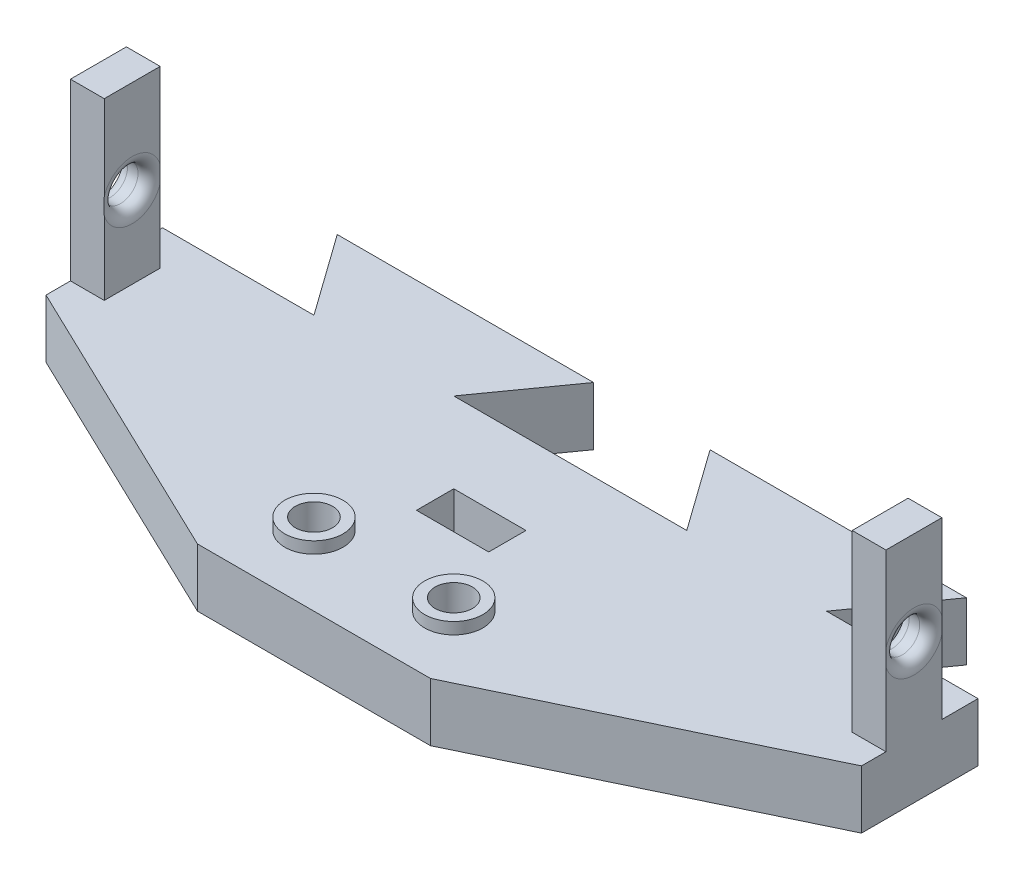
SolidWorks part; units mm, degrees
ref_plane "Front Plane" through (0, 0, 0) normal (0, 0, 1) x (1, 0, 0)
ref_plane "Top Plane" through (0, 0, 0) normal (0, 1, 0) x (1, 0, 0)
ref_plane "Right Plane" through (0, 0, 0) normal (1, 0, 0) x (0, 0, -1)
sketch "Sketch1" plane through (0, 0, 0) normal (0, 1, 0) x (1, 0, 0)
  line L0 (0, 0) -> (20, 0)
  line L1 (10, 0) -> (10, 12) construction
  line L2 (10, 12) -> (-25, 12) construction
  line L3 (0, 0) -> (-25, 12)
  line L4 (-25, 12) -> (-25, 22)
  line L5 (-25, 22) -> (45, 22)
  line L6 (45, 22) -> (45, 12)
  line L7 (45, 12) -> (20, 0)
  dimension "D1" = 35
  dimension "D2" = 20
  dimension "D3" = 12
  dimension "D4" = 70
  dimension "D5" = 10
  dimension "D6" = 10
extrude "Boss-Extrude1" add sketch "Sketch1" along normal blind 5
sketch "Sketch2" plane through (0, 5, 0) normal (0, 1, 0) x (1, 0, 0)
  line L0 (10, 0) -> (10, 22) construction
  line L1 (0, 0) -> (20, 0) construction
  line L2 (45, 22) -> (-25, 22) construction
  circle A0 centre (4, 6) radius 1.6
  circle A1 centre (16, 6) radius 1.6
  dimension "D1" = 3.2
  dimension "D2" = 6
  dimension "D3" = 6
extrude "Cut-Extrude1" cut sketch "Sketch2" against normal blind 3
ref_plane "Plane1" through (0, 0, -6) normal (0, 0, 1) x (1, 0, 0)
sketch "Sketch9" plane through (0, 5, 0) normal (0, 1, 0) x (1, 0, 0)
  line L0 (10, 0) -> (10, 22) construction
  line L1 (0, 0) -> (20, 0) construction
  line L2 (45, 22) -> (-25, 22) construction
  line L3 (10, 11.9) -> (-25, 11.9) construction
  line L4 (-25, 22) -> (-25, 12) construction
  line L5 (-2.75, 6) -> (2.75, 6) construction
  line L7 (6.9, 11.9) -> (13.1, 11.9)
  line L8 (6.9, 11.9) -> (6.9, 15.1)
  line L9 (6.9, 15.1) -> (13.1, 15.1)
  line L10 (13.1, 11.9) -> (13.1, 15.1)
  dimension "D1" = 5.9
  dimension "D2" = 3.1
  dimension "D3" = 3.1
  dimension "D4" = 3.2
sketch "Sketch10" plane through (0, 5, 0) normal (0, 1, 0) x (1, 0, 0)
  line L0 (-25, 22) -> (-25, 12) construction
  line L1 (-25, 18.9) -> (-22.1, 18.9)
  line L2 (-25, 18.9) -> (-25, 14.1)
  line L3 (-25, 14.1) -> (-22.1, 14.1)
  line L4 (-22.1, 18.9) -> (-22.1, 14.1)
  line L5 (45, 22) -> (-25, 22) construction
  line L6 (10, 22) -> (10, 0) construction
  line L7 (0, 0) -> (20, 0) construction
  line L8 (45, 14.1) -> (42.1, 14.1)
  line L9 (42.1, 18.9) -> (42.1, 14.1)
  line L10 (45, 18.9) -> (42.1, 18.9)
  line L11 (45, 18.9) -> (45, 14.1)
  dimension "D1" = 3.1
  dimension "D2" = 4.8
  dimension "D3" = 2.9
extrude "Boss-Extrude2" add sketch "Sketch10" along normal blind 15
extrude "Cut-Extrude4" cut sketch "Sketch9" against normal blind 5
sketch "Sketch11" plane through (-25, 0, 0) normal (-1, 0, 0) x (0, 0, 1)
  circle A0 centre (-16.5, 12) radius 1.5
  dimension "D1" = 3
  dimension "D2" = 7
extrude "Cut-Extrude5" cut sketch "Sketch11" against normal blind 70
fillet "Fillet3" radius 1 1 edges at (-25, 12, -15)
fillet "Fillet4" radius 1 1 edges at (-22.1, 12, -15)
fillet "Fillet6" radius 1 1 edges at (42.1, 12, -18)
fillet "Fillet7" radius 1 1 edges at (45, 12, -15)
sketch "Sketch13" plane through (0, 5, 0) normal (0, 1, 0) x (1, 0, 0)
  line L0 (-12, 22) -> (-17, 29)
  line L1 (45, 22) -> (-25, 22) construction
  line L2 (-17, 29) -> (5, 29)
  line L3 (5, 29) -> (0, 22)
  line L4 (10, 22) -> (10, 29) construction
  line L5 (15, 29) -> (20, 22)
  line L6 (37, 29) -> (15, 29)
  line L7 (32, 22) -> (37, 29)
  line L8 (-12, 22) -> (0, 22)
  line L9 (20, 22) -> (32, 22)
  dimension "D1" = 5
  dimension "D2" = 8
  dimension "D3" = 12
  dimension "D4" = 5
  dimension "D5" = 7
extrude "Boss-Extrude4" add sketch "Sketch13" against normal blind 5
sketch "Sketch14" plane through (0, 5, 0) normal (0, 1, 0) x (1, 0, 0)
  circle A0 centre (4, 6) radius 2.5
  circle A1 centre (16, 6) radius 2.5
  circle A2 centre (16, 6) radius 1.6
  circle A3 centre (4, 6) radius 1.6
  dimension "D1" = 5
  dimension "D2" = 5
extrude "Boss-Extrude5" add sketch "Sketch14" along normal blind 1
